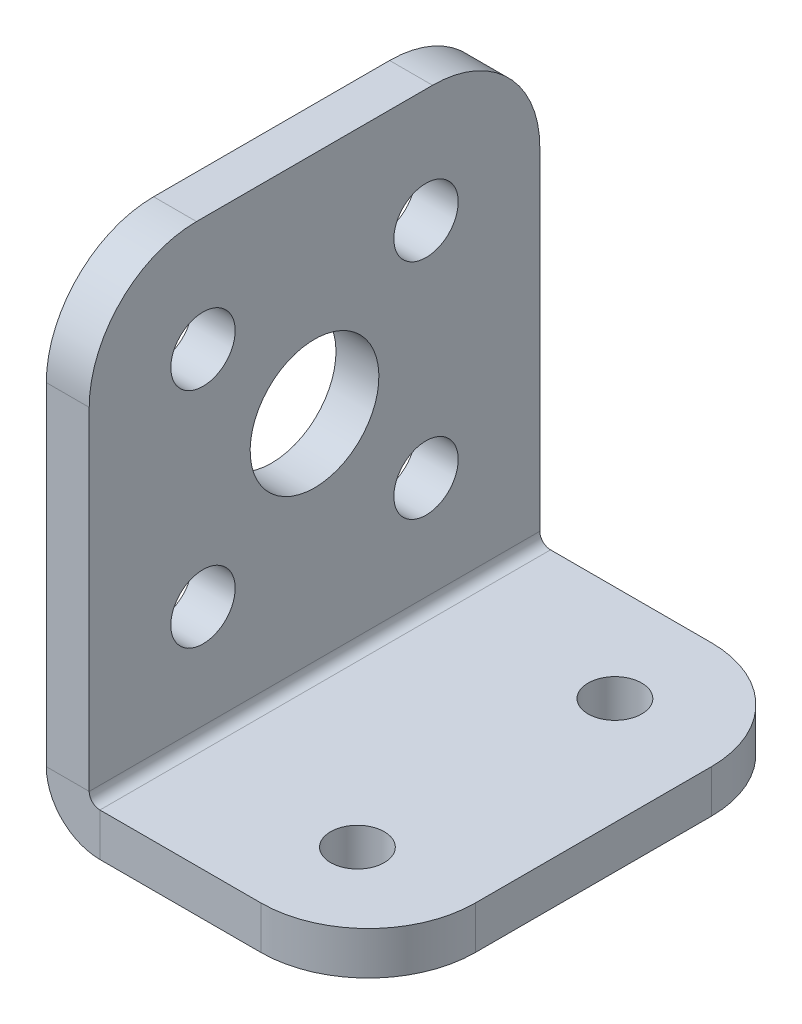
SolidWorks part; units mm, degrees
note: The reader was unsure of these and kept them because the rebuilt part matched: flange length of "Brida de arista1".
material "Aleación 6061"
ref_plane "Alzado" through (0, 0, 0) normal (0, 0, 1) x (1, 0, 0)
ref_plane "Planta" through (0, 0, 0) normal (0, 1, 0) x (1, 0, 0)
ref_plane "Vista lateral" through (0, 0, 0) normal (1, 0, 0) x (0, 0, -1)
sketch "Croquis base" plane through (0, 0, 0) normal (1, 0, 0) x (0, -1, 0)
  line L1 (-10.25, 10.5) -> (10.25, 10.5)
  line L2 (-10.25, 10.5) -> (-10.25, -10.5)
  line L3 (-10.25, -10.5) -> (10.25, -10.5)
  line L4 (10.25, 10.5) -> (10.25, -10.5)
  line L5 (-10.25, 10.5) -> (10.25, -10.5) construction
  line L6 (-10.25, -10.5) -> (10.25, 10.5) construction
  point P0 (0, 0)
  point P6 (10.25, 0)
  dimension "D1" = 20.5
  dimension "D2" = 21
base flange "Brida base1" sketch "Croquis base" thickness 2 reverse thickness direction no parameters "D1"=0.7366
edge flange "Brida de arista1" sketch "Croquis10" flange angle 90 flange length 13 flange position bend outside bend radius 0.5 thickness 2 relief rectangular parameters "D6"=10
sketch "Croquis10" plane through (0, -10.25, 0) normal (0, -1, 0) x (0, 0, -1)
  line L2 (-10.5, 0) -> (-10.5, 13)
  line L3 (-10.5, 13) -> (10.5, 13)
  line L4 (10.5, 13) -> (10.5, 0)
  line L7 (-10.5, 0) -> (10.5, 0) construction
  line L8 (-10.5, 0) -> (10.5, 0)
bend "Pliegue de arista1" bend radius 0.5 bend angle 90 parameters "D5"=1
sketch "Croquis11" plane through (-2, 0, 0) normal (-1, 0, 0) x (0, -1, 0)
  line L0 (-10.25, -10.5) -> (-10.25, 10.5) construction
  line L1 (-10.25, 0) -> (10.25, 0) construction
  line L2 (10.25, 10.5) -> (10.25, -10.5) construction
  line L4 (0.25, 0) -> (-4.836, 5.086) construction
  line L5 (0.25, 0) -> (-4.9472, 5.1972) construction
  line L6 (0.25, 0) -> (5.4472, 5.1972) construction
  circle A2 centre (0.25, 0) radius 3
  circle A3 centre (-4.9472, 5.1972) radius 1.5
  circle A4 centre (5.4472, 5.1972) radius 1.5
  circle A5 centre (5.4472, -5.1972) radius 1.5
  circle A6 centre (-4.9472, -5.1972) radius 1.5
  dimension "D3" = 7.35
  dimension "D2" = 45
  dimension "D4" = 4
  dimension "D1" = 10.5
  dimension "D5" = 90
extrude "Cortar-Extruir1" cut sketch "Croquis11" against normal blind 10
sketch "Croquis12" plane through (0, -12.75, 0) normal (0, -1, 0) x (0, 0, -1)
  line L0 (-10.5, 8) -> (10.5, 8) construction
  line L1 (-10.5, 13) -> (-10.5, 0.5) construction
  line L2 (10.5, 0.5) -> (10.5, 13) construction
  line L3 (10.5, 13) -> (-10.5, 13) construction
  line L4 (0, 13) -> (0, 0.5) construction
  line L5 (10.5, 0.5) -> (-10.5, 0.5) construction
  circle A0 centre (6, 8) radius 1.25
  circle A1 centre (-6, 8) radius 1.25
  point P14 (0, 8)
  dimension "D1" = 5
  dimension "D2" = 6
extrude "Cortar-Extruir2" cut sketch "Croquis12" against normal blind 2 normal cut yes
fillet "Redondeo1" radius 5 4 edges at (-1, 10.25, 10.5) (-1, 10.25, -10.5) (13, -11.75, -10.5) (13, -11.75, 10.5)
sketch "Líneas de pliegue1" [suppressed] plane through (0, 0, 0) normal (0, 1, 0) x (1, 0, 0)
sketch "Cuadro delimitador1" [suppressed] plane through (0, 0, 0) normal (0, 1, 0) x (1, 0, 0)
sheet metal parameters "Chapa metálica1" thickness 2 parameters "D1"=0.7366
flat pattern "Chapa desplegada1" [suppressed]
sketch "Líneas de pliegue2" plane through (0, 0, 0) normal (0, 1, 0) x (1, 0, 0)
sketch3d "Cuadro delimitador2" [suppressed]
  line L0 (10.25, 10.5, 0) -> (10.25, -10.5, 0) construction
  line L1 (-10.25, 10.5, 0) -> (-10.25, -10.5, 0) construction
  line L2 (10.25, 10.5, 0) -> (-10.25, 10.5, 0) construction
  line L3 (10.25, -10.5, 0) -> (-10.25, -10.5, 0) construction
sheet metal parameters "Chapa metálica2" thickness 2 parameters "D1"=0.7366
flat pattern "Chapa desplegada1"
sketch "Líneas de pliegue2" plane through (0, 0, 0) normal (0, 1, 0) x (1, 0, 0)
  line L0 (11.4281, -10.5) -> (11.4281, 10.5) construction
  line L1 (11.4281, -10.5) -> (11.4281, 10.5) construction
sketch3d "Cuadro delimitador2" [suppressed]
  line L0 (25.1062, -10.5, 0) -> (-10.25, -10.5, 0) construction
  line L1 (25.1062, 10.5, 0) -> (-10.25, 10.5, 0) construction
  line L2 (25.1062, -10.5, 0) -> (25.1062, 10.5, 0) construction
  line L3 (-10.25, -10.5, 0) -> (-10.25, 10.5, 0) construction
bend of the flat pattern "Aplanar-<Pliegue de arista1>1"
sheet metal parameters "Chapa metálica3" thickness 2 parameters "D1"=0.7366
flat pattern "Chapa desplegada1"
sketch "Líneas de pliegue2" plane through (0, 0, 0) normal (0, 1, 0) x (1, 0, 0)
  line L0 (11.4281, -10.5) -> (11.4281, 10.5) construction
  line L1 (11.4281, -10.5) -> (11.4281, 10.5) construction
sketch3d "Cuadro delimitador2" [suppressed]
  line L0 (25.1062, -10.5, 0) -> (-10.25, -10.5, 0) construction
  line L1 (25.1062, 10.5, 0) -> (-10.25, 10.5, 0) construction
  line L2 (25.1062, -10.5, 0) -> (25.1062, 10.5, 0) construction
  line L3 (-10.25, -10.5, 0) -> (-10.25, 10.5, 0) construction
bend of the flat pattern "Aplanar-<Pliegue de arista1>1"
sheet metal parameters "Chapa metálica4" thickness 2 parameters "D1"=0.7366
flat pattern "Chapa desplegada1"
sketch "Líneas de pliegue2" plane through (0, 0, 0) normal (1, 0, 0) x (0, 0, -1)
  line L0 (-10.5, -11.4281) -> (10.5, -11.4281) construction
  line L1 (-10.5, -11.4281) -> (10.5, -11.4281) construction
sketch3d "Cuadro delimitador2" [suppressed]
  line L0 (10.5, -25.1062, 0) -> (10.5, 10.25, 0) construction
  line L1 (-10.5, -25.1062, 0) -> (-10.5, 10.25, 0) construction
  line L2 (10.5, -25.1062, 0) -> (-10.5, -25.1062, 0) construction
  line L3 (10.5, 10.25, 0) -> (-10.5, 10.25, 0) construction
bend of the flat pattern "Aplanar-<Pliegue de arista1>1"
